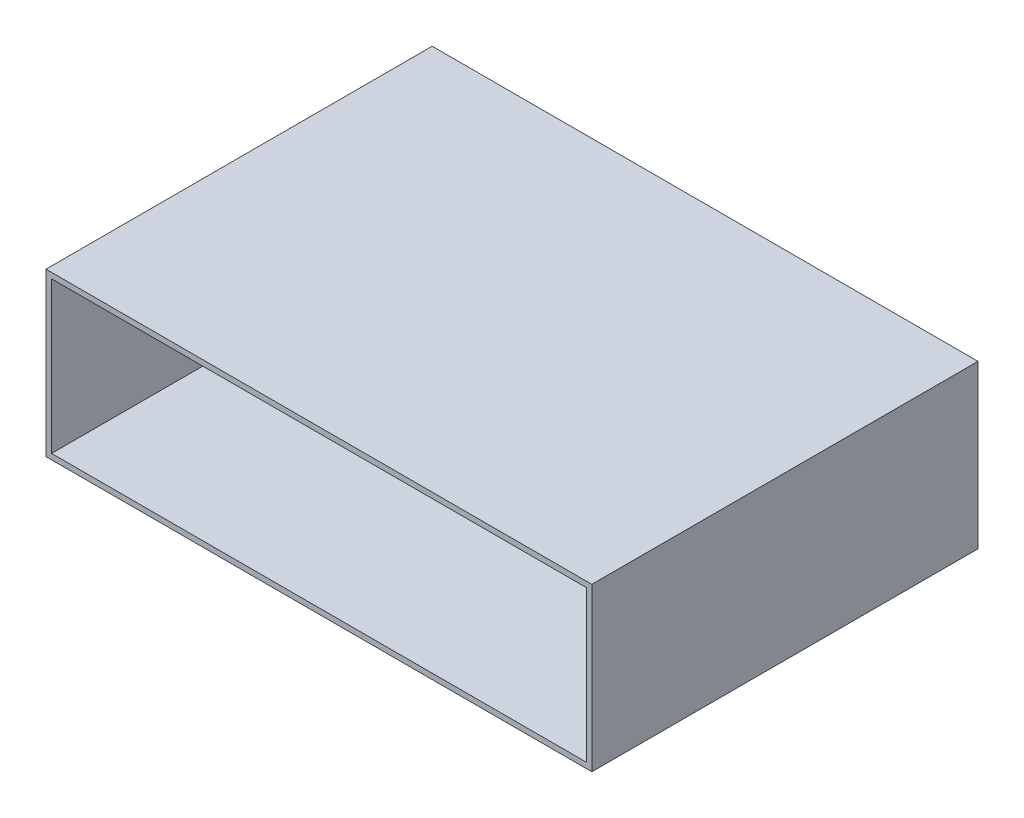
SolidWorks part; units mm, degrees
material "Custom Plastic"
ref_plane "X-Y Datum" through (0, 0, 0) normal (0, 0, 1) x (1, 0, 0)
ref_plane "X-Z Datum" through (0, 0, 0) normal (0, 1, 0) x (1, 0, 0)
ref_plane "Y-Z Datum" through (0, 0, 0) normal (1, 0, 0) x (0, 0, -1)
sketch "Sketch1" plane through (0, 0, 0) normal (0, 0, 1) x (1, 0, 0)
  line L1 (-152.2312, -43.0525) -> (152.2312, -43.0525)
  line L2 (-152.2312, -43.0525) -> (-152.2312, 43.0525)
  line L3 (-152.2312, 43.0525) -> (152.2312, 43.0525)
  line L4 (152.2312, -43.0525) -> (152.2312, 43.0525)
  line L5 (-152.2312, -43.0525) -> (152.2312, 43.0525) construction
  line L6 (-152.2312, 43.0525) -> (152.2312, -43.0525) construction
  line L7 (-155.4062, -46.2275) -> (155.4063, -46.2275)
  line L8 (-155.4062, -46.2275) -> (-155.4062, 46.2275)
  line L9 (-155.4062, 46.2275) -> (155.4063, 46.2275)
  line L10 (155.4063, -46.2275) -> (155.4063, 46.2275)
  line L11 (-155.4062, -46.2275) -> (155.4063, 46.2275) construction
  line L12 (-155.4062, 46.2275) -> (155.4063, -46.2275) construction
  point P0 (0, 0)
  point P6 (0, 0)
  dimension "D1" = 3.175
  dimension "D2" = 3.175
  dimension "D3" = 310.8125
  dimension "D4" = 92.455
extrude "Boss-Extrude1" add sketch "Sketch1" along normal blind 219.9
extrude "Boss-Extrude2" add sketch "Sketch1<2>" along normal blind 3.175 contours L1 L4 L3 L2 region at (0, 0, 0)
sketch "Sketch1<2>" plane through (0, 0, 0) normal (0, 0, 1) x (1, 0, 0) same geometry as "Sketch1"
sketch "Sketch3" plane through (0, 43.0525, 0) normal (0, -1, 0) x (1, 0, 0)
  line L0 (0, 0) -> (0, 127)
  line L1 (155.4063, 127) -> (-155.4062, 127)
  line L2 (155.4063, 219.9) -> (155.4063, 0) construction
  line L3 (-155.4062, 219.9) -> (-155.4062, 0) construction
  line L4 (17.6715, 0) -> (17.6715, 88.9)
  line L5 (155.4063, 88.9) -> (-155.4062, 88.9)
  dimension "D1" = 127
  dimension "D2" = 88.9
